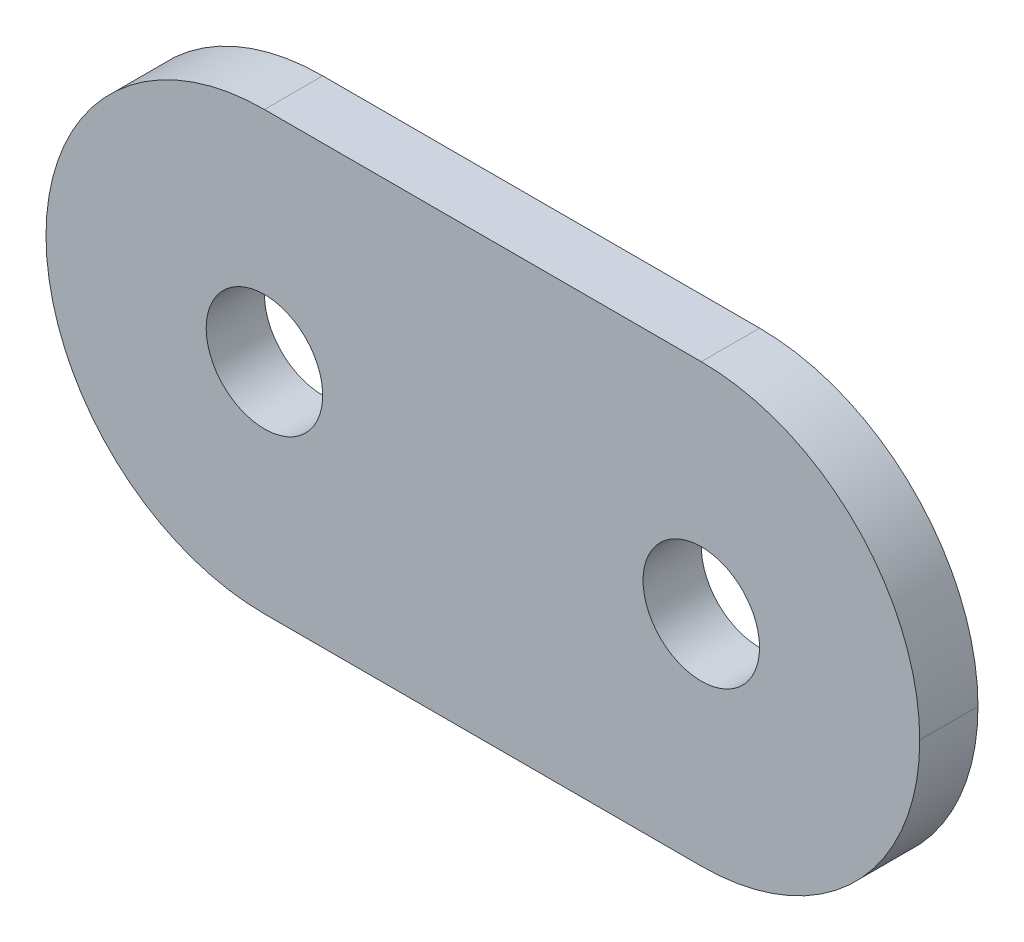
SolidWorks part; units mm, degrees
material "Thornel Mat VMA"
ref_plane "前视基准面" through (0, 0, 0) normal (0, 0, 1) x (1, 0, 0)
ref_plane "上视基准面" through (0, 0, 0) normal (0, 1, 0) x (1, 0, 0)
ref_plane "右视基准面" through (0, 0, 0) normal (1, 0, 0) x (0, 0, -1)
sketch "草图1" plane through (0, 0, 0) normal (0, 0, 1) x (1, 0, 0)
  line L1 (-15, -7.5) -> (15, -7.5)
  line L2 (-15, -7.5) -> (-15, 7.5)
  line L3 (-15, 7.5) -> (15, 7.5)
  line L4 (15, -7.5) -> (15, 7.5)
  line L5 (-15, -7.5) -> (15, 7.5) construction
  line L6 (-15, 7.5) -> (15, -7.5) construction
  point P0 (0, 0)
  dimension "D1" = 15
  dimension "D2" = 30
extrude "凸台-拉伸1" add sketch "草图1" along normal blind 2
fillet "圆角1" radius 7.5 4 edges at (15, -7.5, 1) (-15, -7.5, 1) (-15, 7.5, 1) (15, 7.5, 1)
sketch "草图2" plane through (0, 0, 2) normal (0, 0, 1) x (1, 0, 0)
  line L0 (0, 3.751) -> (0, -2.5735) construction
  circle A0 centre (7.5, 0) radius 2
  circle A1 centre (-7.5, 0) radius 2
  dimension "D1" = 4
extrude "切除-拉伸1" cut sketch "草图2" against normal blind 2
